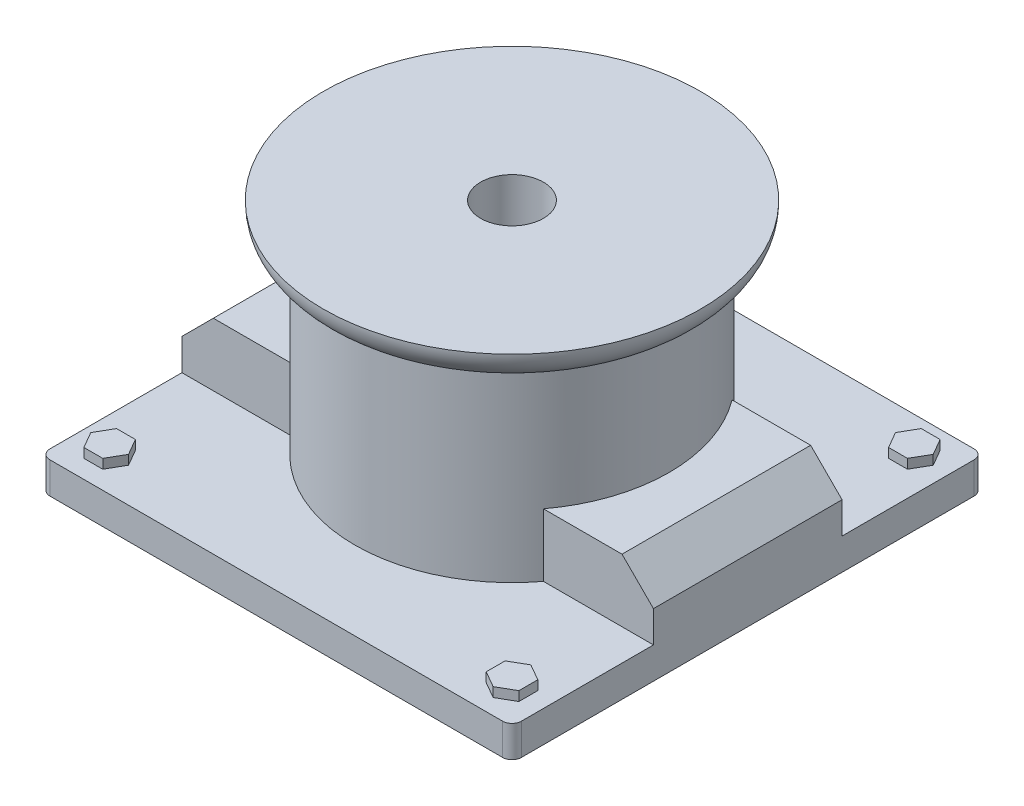
SolidWorks part; units mm, degrees
ref_plane "Front Plane" through (0, 0, 0) normal (0, 0, 1) x (1, 0, 0)
ref_plane "Top Plane" through (0, 0, 0) normal (0, 1, 0) x (1, 0, 0)
ref_plane "Right Plane" through (0, 0, 0) normal (1, 0, 0) x (0, 0, -1)
sketch "Sketch1" plane through (0, 0, 0) normal (0, 1, 0) x (1, 0, 0)
  line L1 (-75, 75) -> (75, 75)
  line L2 (-75, 75) -> (-75, -75)
  line L3 (-75, -75) -> (75, -75)
  line L4 (75, 75) -> (75, -75)
  line L5 (-75, 75) -> (75, -75) construction
  line L6 (-75, -75) -> (75, 75) construction
  point P0 (0, 0)
  dimension "D1" = 150
  dimension "D2" = 150
extrude "Boss-Extrude1" add sketch "Sketch1" along normal blind 10
sketch "Sketch2" plane through (0, 10, 0) normal (0, 1, 0) x (1, 0, 0)
  circle A0 centre (0, 0) radius 50
  dimension "D1" = 100
extrude "Boss-Extrude2" add sketch "Sketch2" along normal blind 60 contours A0
sketch "Sketch3" plane through (0, 70, 0) normal (0, 1, 0) x (1, 0, 0)
  circle A0 centre (0, 0) radius 60
  dimension "D1" = 120
extrude "Boss-Extrude3" add sketch "Sketch3" along normal blind 10
sketch "Sketch7" plane through (0, 0, 0) normal (0, -1, 0) x (-1, 0, 0)
  line L0 (-75, -75) -> (-75, 75) construction
  line L1 (75, -30) -> (-75, -30)
  line L2 (75, -30) -> (75, 30)
  line L3 (75, 30) -> (-75, 30)
  line L4 (-75, -30) -> (-75, 30)
  line L5 (75, -30) -> (-75, 30) construction
  line L6 (75, 30) -> (-75, -30) construction
  point P0 (0, 0)
  dimension "D1" = 60
extrude "Boss-Extrude6" add sketch "Sketch7" against normal blind 30 contours L2 L1 L4 L3
sketch "Sketch8" plane through (0, 80, 0) normal (0, 1, 0) x (1, 0, 0)
  circle A0 centre (0, 0) radius 10
  dimension "D1" = 20
extrude "Cut-Extrude2" cut sketch "Sketch8" against normal blind 20 contours A0
fillet "Fillet3" radius 10 1 edges at (0, 70, 60)
fillet "Fillet4" radius 3 4 edges at (-75, 5, 75) (-75, 5, -75) (75, 5, -75) (75, 5, 75)
chamfer "Chamfer1" distance 10 angle 45 2 edges at (75, 30, 0) (-75, 30, 0)
sketch "Sketch9" plane through (0, 10, 0) normal (0, 1, 0) x (1, 0, 0)
  line L0 (-74.1213, -74.1213) -> (0, 0) construction
  line L2 (-57.9931, -63.9931) -> (-60.9931, -58.797)
  line L3 (-60.9931, -58.797) -> (-66.9931, -58.797)
  line L4 (-66.9931, -58.797) -> (-69.9931, -63.9931)
  line L5 (-69.9931, -63.9931) -> (-66.9931, -69.1893)
  line L6 (-66.9931, -69.1893) -> (-60.9931, -69.1893)
  line L7 (-60.9931, -69.1893) -> (-57.9931, -63.9931)
  arc A0 (-75, -72) -> (-72, -75) centre (-72, -72) ccw construction
  circle A1 centre (-63.9931, -63.9931) radius 5.1962 construction
  dimension "D1" = 6
extrude "Boss-Extrude7" add sketch "Sketch9" along normal blind 3
pattern_circular "CirPattern1" count 4 every 90 about axis through (0, 80, 0) along (0, 1, 0) of "Boss-Extrude7"
